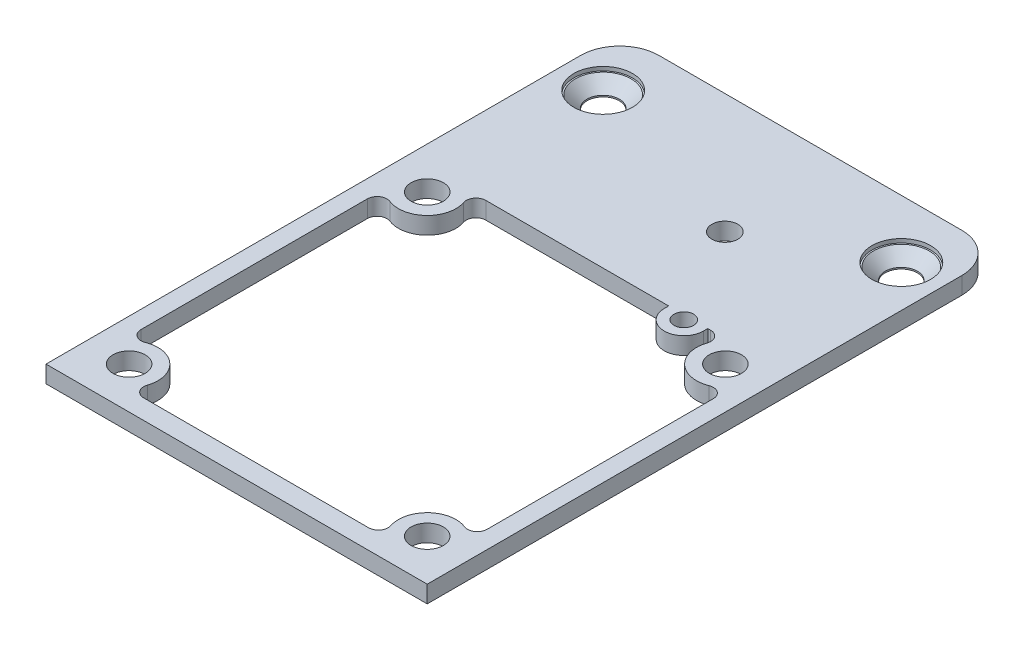
SolidWorks part; units mm, degrees
ref_plane "Front Plane" through (0, 0, 0) normal (0, 0, 1) x (1, 0, 0)
ref_plane "Top Plane" through (0, 0, 0) normal (0, 1, 0) x (1, 0, 0)
ref_plane "Right Plane" through (0, 0, 0) normal (1, 0, 0) x (0, 0, -1)
sketch "Sketch1" plane through (0, 0, 0) normal (0, 1, 0) x (1, 0, 0)
  line L0 (-15.5, 39.2) -> (15.5, 39.2)
  line L1 (-18.2, 15) -> (-18.2, -15) construction
  line L2 (17.7, -17.4996) -> (-17.7, -17.4996)
  line L3 (17.7, -17.4996) -> (17.7, 17.4996)
  line L4 (17.7, 17.4996) -> (-17.7, 17.4996)
  line L5 (-17.7, -17.4996) -> (-17.7, 17.4996)
  line L6 (17.7, -17.4996) -> (-17.7, 17.4996) construction
  line L7 (-19.5, 35.2) -> (-19.5, -19.5)
  line L8 (-19.5, -19.5) -> (19.5, -19.5)
  line L9 (19.5, -19.5) -> (19.5, 35.2)
  line L10 (17.7, 17.4996) -> (-17.7, -17.4996) construction
  line L11 (-15.25, 15.25) -> (-15.25, 17.9996) construction
  line L12 (11.2, 17.05) -> (11.2, 17.4996)
  line L13 (7.2, 17.05) -> (7.2, 17.4996)
  arc A0 (19.5, 35.2) -> (15.5, 39.2) centre (15.5, 35.2) ccw construction
  arc A1 (-15.5, 39.2) -> (-19.5, 35.2) centre (-15.5, 35.2) ccw construction
  arc A2 (19.5, 35.2) -> (15.5, 39.2) centre (15.5, 35.2) ccw
  arc A3 (-15.5, 39.2) -> (-19.5, 35.2) centre (-15.5, 35.2) ccw
  circle A4 centre (-15.25, -15.25) radius 1.65 construction
  circle A5 centre (15.25, -15.25) radius 1.65 construction
  circle A6 centre (-15.25, 15.25) radius 1.65 construction
  circle A7 centre (15.25, 15.25) radius 1.65 construction
  circle A8 centre (-15.25, 33.25) radius 1.65 construction
  circle A9 centre (15.25, 33.25) radius 1.65 construction
  circle A10 centre (-15.25, -15.25) radius 1.65
  circle A11 centre (15.25, -15.25) radius 1.65
  circle A12 centre (-15.25, 15.25) radius 1.65
  circle A13 centre (15.25, 15.25) radius 1.65
  circle A14 centre (-15.25, 33.25) radius 1.65
  circle A15 centre (15.25, 33.25) radius 1.65
  arc A16 (-15.2, 18) -> (-18.2, 15) centre (-15.2, 15) ccw construction
  circle A17 centre (-15.25, 15.25) radius 2.95
  circle A18 centre (15.25, 15.25) radius 2.95
  circle A19 centre (-15.25, -15.25) radius 2.95
  circle A20 centre (15.25, -15.25) radius 2.95
  circle A21 centre (3.5, 26.95) radius 1.33 construction
  circle A22 centre (9.2, 17.05) radius 2
  circle A23 centre (9.2, 17.05) radius 1
  circle A24 centre (9.2, 17.05) radius 0.9 construction
  circle A25 centre (3.5, 26.95) radius 1.33
  point P29 (0, 0)
  dimension "D3" = 2
  dimension "D4" = 1
  dimension "D1" = 0.5
  dimension "D2" = 0.5
extrude "Base shape" add sketch "Sketch1" along normal blind 1.75 contours L0 A3 L7 L8 L9 A2 A20 L3 L2 A19 L5 A17 L4 A18 A15 A14 | A17 L4 L5 | L4 A17 L5 A12 | L5 A17 | L4 A17 | L3 A18 L4 A13 | L3 A18 | L4 A18 | L2 A19 L5 A10 | L2 A19 | L5 A19 | A19 L5 L2 | L2 A20 L3 A11 | L3 A20 | L2 A20 | A20 L2 L3 | A18 L3 L4 | A23 L4 A22 | A23 L4 A22 | A22 L4 L13 | A22 L12 L4 region at (-0.0606, 0, -21.3897) region at (17.5279, 0, 17.307) region at (15.25, 0, 17.7828) region at (15.25, 0, 17.4246) region at (17.9015, 0, 15.25) region at (-15.25, 0, 17.7828) region at (-15.25, 0, 17.4246) region at (13.3348, 0, -13.1057) region at (17.9015, 0, -15.25) region at (-17.5279, 0, 17.307) region at (17.5279, 0, -17.307) region at (15.25, 0, -17.7828) region at (-17.9015, 0, 15.25) region at (11.1847, 0, -17.3875) region at (-17.9015, 0, -15.25) region at (-17.625, 0, -15.25) region at (11.1406, 0, -17.2709) region at (9.2, 0, -18.2243) region at (-17.5279, 0, -17.307) region at (7.2153, 0, -17.3875) region at (-15.25, 0, -17.7828)
fillet "Milling fillets" radius 1 8 edges at (-17.7, 0.875, 13.6068) (-13.3416, 0.875, 17.4996) (13.3416, 0.875, 17.4996) (17.7, 0.875, 13.6068) (17.7, 0.875, -13.6068) (13.3416, 0.875, -17.4996) (-13.3416, 0.875, -17.4996) (-17.7, 0.875, -13.6068)
sketch "Sketch3" plane through (0, 1.75, 0) normal (0, 1, 0) x (1, 0, 0)
  circle A0 centre (-15.25, 33.25) radius 3
  circle A1 centre (15.25, 33.25) radius 3
  dimension "D1" = 6
extrude "Screw head cut" cut sketch "Sketch3" against normal blind 0.4
chamfer "Screw head chamfer" distance 1.2 angle 45 2 edges at (15.25, 1.35, -31.6) (-15.25, 1.35, -31.6)
